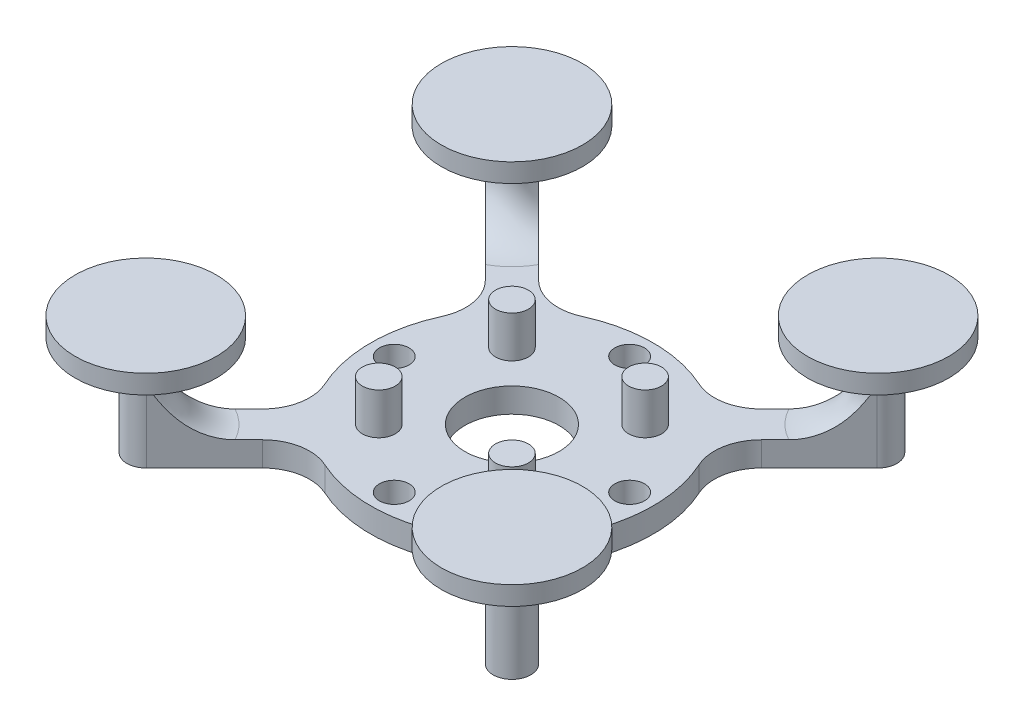
SolidWorks part; units mm, degrees
material "Acrylic (Medium-high impact)"
ref_plane "Front Plane" through (0, 0, 0) normal (0, 0, 1) x (1, 0, 0)
ref_plane "Top Plane" through (0, 0, 0) normal (0, 1, 0) x (1, 0, 0)
ref_plane "Right Plane" through (0, 0, 0) normal (1, 0, 0) x (0, 0, -1)
ref_axis "Axis1" through (-33.0333, 0, 0) along (1, 0, 0)
ref_axis "Axis2" through (0, 24.5224, 0) along (0, -1, 0)
ref_axis "Axis3" through (0, 0, -30.7663) along (0, 0, 1)
sketch "Sketch1" plane through (0, 0, 0) normal (0, 1, 0) x (1, 0, 0)
  line L0 (0, 12.5) -> (0, -12.5) construction
  line L1 (-12.5, 0) -> (12.5, 0) construction
  circle A0 centre (0, 0) radius 15
  circle A1 centre (0, 12.5) radius 1.575
  circle A2 centre (12.5, 0) radius 1.575
  circle A3 centre (0, -12.5) radius 1.575
  circle A4 centre (-12.5, 0) radius 1.575
  circle A5 centre (0, 0) radius 5
  point P7 (0, 0)
  point P8 (0, 0)
  dimension "D1" = 25
  dimension "D2" = 25
  dimension "D3" = 3.15
  dimension "D4" = 30
  dimension "D5" = 10
extrude "Boss-Extrude1" add sketch "Sketch1" along normal blind 2.6
sketch "Sketch2" plane through (0, 2.6, 0) normal (0, 1, 0) x (1, 0, 0)
  line L0 (-7.0711, 7.0711) -> (7.0711, -7.0711) construction
  line L1 (-7.0711, -7.0711) -> (7.0711, 7.0711) construction
  line L2 (0, 0) -> (0, 3.175) construction
  circle A0 centre (0, 0) radius 10 construction
  circle A1 centre (-7.0711, 7.0711) radius 1.75
  circle A2 centre (7.0711, 7.0711) radius 1.75
  circle A3 centre (7.0711, -7.0711) radius 1.75
  circle A4 centre (-7.0711, -7.0711) radius 1.75
  point P7 (0, 0)
  point P8 (0, 0)
  dimension "D1" = 20
  dimension "D3" = 3.5
  dimension "D2" = 45
extrude "Boss-Extrude2" add sketch "Sketch2" along normal blind 4.4
sketch "Sketch3" plane through (0, 2.6, 0) normal (0, 1, 0) x (1, 0, 0)
  line L0 (-19.4454, 19.4454) -> (19.4454, -19.4454) construction
  line L1 (-19.4454, -19.4454) -> (19.4454, 19.4454) construction
  line L2 (0, 0) -> (0, 2.54) construction
  line L3 (-20.8082, 17.9797) -> (-11.9261, 9.0977)
  line L4 (-17.9797, 20.8082) -> (-9.0977, 11.9261)
  line L5 (-16.3671, 13.5387) -> (-13.5387, 16.3671) construction
  line L18 (17.9797, 20.8082) -> (9.0977, 11.9261)
  line L19 (20.8082, 17.9797) -> (11.9261, 9.0977)
  line L20 (20.8082, -17.9797) -> (11.9261, -9.0977)
  line L21 (17.9797, -20.8082) -> (9.0977, -11.9261)
  line L22 (-17.9797, -20.8082) -> (-9.0977, -11.9261)
  line L23 (-20.8082, -17.9797) -> (-11.9261, -9.0977)
  circle A0 centre (0, 0) radius 27.5 construction
  circle A1 centre (0, 0) radius 15 construction
  arc A5 (-11.9261, 9.0977) -> (-9.0977, 11.9261) centre (0, 0) cw
  arc A12 (-17.9797, 20.8082) -> (-20.8082, 17.9797) centre (-19.4454, 19.4454) ccw
  arc A19 (9.0977, 11.9261) -> (11.9261, 9.0977) centre (0, 0) cw
  arc A20 (20.8082, 17.9797) -> (17.9797, 20.8082) centre (19.4454, 19.4454) ccw
  arc A21 (11.9261, -9.0977) -> (9.0977, -11.9261) centre (0, 0) cw
  arc A22 (17.9797, -20.8082) -> (20.8082, -17.9797) centre (19.4454, -19.4454) ccw
  arc A23 (-9.0977, -11.9261) -> (-11.9261, -9.0977) centre (0, 0) cw
  arc A24 (-20.8082, -17.9797) -> (-17.9797, -20.8082) centre (-19.4454, -19.4454) ccw
  point P7 (0, 0)
  point P8 (0, 0)
  point P20 (-14.9529, 14.9529)
  point P36 (0, 0)
  point P39 (2.8584, -2.8584)
  point P43 (0, 0)
  dimension "D1" = 55
  dimension "D3" = 4
  dimension "D4" = 4
  dimension "D2" = 45
extrude "Boss-Extrude3" add sketch "Sketch3" against normal up to surface (2.6 mm away) up to face at (0, 0, 15)
sketch "Sketch5" plane through (0, 2.6, 0) normal (0, 1, 0) x (1, 0, 0)
  circle A4 centre (-19.4454, 19.4454) radius 2.0011
  circle A5 centre (19.4454, 19.4454) radius 2.0011
  circle A6 centre (19.4454, -19.4454) radius 2.0011
  circle A7 centre (-19.4454, -19.4454) radius 2.0011
extrude "Boss-Extrude4" add sketch "Sketch5" along normal blind 10
sketch "Sketch6" plane through (0, 12.6, 0) normal (0, 1, 0) x (1, 0, 0)
  circle A0 centre (19.4454, -19.4454) radius 7.5
  circle A1 centre (19.4454, 19.4454) radius 7.5
  circle A2 centre (-19.4454, 19.4454) radius 7.5
  circle A3 centre (-19.4454, -19.4454) radius 7.5
  dimension "D1" = 15
extrude "Boss-Extrude5" add sketch "Sketch6" against normal blind 2
fillet "Fillet1" radius 5 8 edges at (-9.0977, 1.3, -11.9261) (-11.9261, 1.3, -9.0977) (-11.9261, 1.3, 9.0977) (11.9261, 1.3, 9.0977) (-9.0977, 1.3, 11.9261) (9.0977, 1.3, 11.9261) (11.9261, 1.3, -9.0977) (9.0977, 1.3, -11.9261)
fillet "Fillet4" radius 5 4 edges at (-19.4454, 2.6, -17.4443) (-19.4454, 2.6, 21.4465) (19.4454, 2.6, 21.4465) (19.4454, 2.6, -17.4443)
fillet "Fillet5" radius 6.5 4 edges at (-19.4454, 10.6, 21.4465) (19.4454, 10.6, 21.4465) (19.4454, 10.6, -17.4443) (-19.4454, 10.6, -17.4443)
